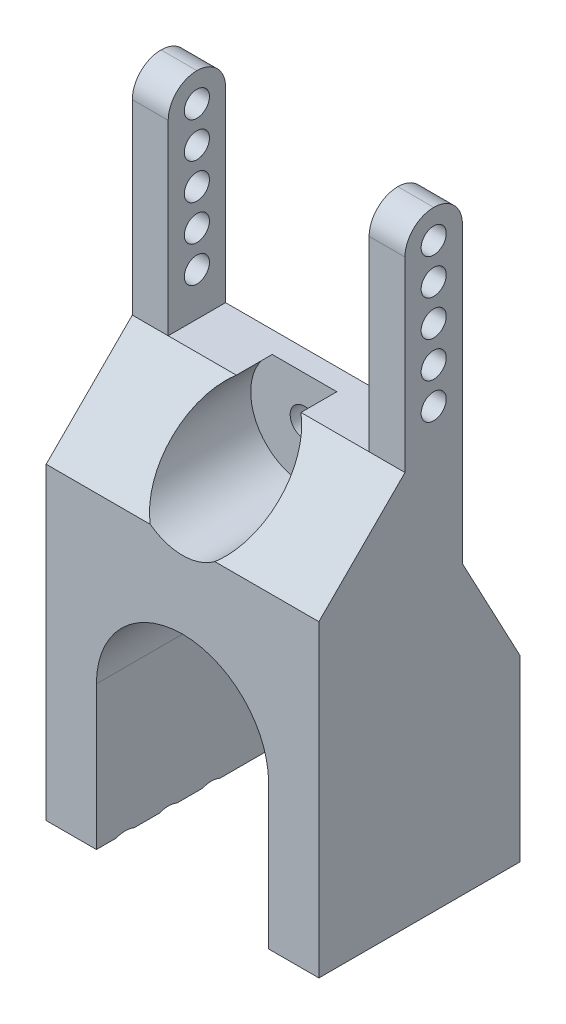
SolidWorks part; units mm, degrees
ref_plane "Front Plane" through (0, 0, 0) normal (0, 0, 1) x (1, 0, 0)
ref_plane "Top Plane" through (0, 0, 0) normal (0, 1, 0) x (1, 0, 0)
ref_plane "Right Plane" through (0, 0, 0) normal (1, 0, 0) x (0, 0, -1)
sketch "Sketch1" plane through (0, 0, 0) normal (0, 0, 1) x (1, 0, 0)
  line L1 (-19, -27.5) -> (19, -27.5)
  line L2 (-19, -27.5) -> (-19, 27.5)
  line L3 (-19, 27.5) -> (19, 27.5)
  line L4 (19, -27.5) -> (19, 27.5)
  line L5 (-19, -27.5) -> (19, 27.5) construction
  line L6 (-19, 27.5) -> (19, -27.5) construction
  point P0 (0, 0)
  dimension "D1" = 38
  dimension "D2" = 55
extrude "Boss-Extrude1" add sketch "Sketch1" along normal blind 20
sketch "Sketch2" plane through (0, 0, 20) normal (0, 0, 1) x (1, 0, 0)
  line L0 (-19, -27.5) -> (19, -27.5) construction
  line L1 (-12, -27.5) -> (12, -27.5)
  line L2 (-12, -27.5) -> (-12, -7.5)
  line L3 (-12, -7.5) -> (12, -7.5) construction
  line L4 (12, -27.5) -> (12, -7.5)
  line L5 (0, -7.5) -> (0, 0) construction
  arc A0 (-12, -7.5) -> (12, -7.5) centre (0, -7.5) cw
  dimension "D1" = 24
  dimension "D2" = 20
extrude "Cut-Extrude1" cut sketch "Sketch2" against normal through all
sketch "Sketch3" plane through (0, -27.5, 0) normal (0, -1, 0) x (1, 0, 0)
  line L0 (-15, 16) -> (15, 16) construction
  line L1 (0, 16) -> (0, 0) construction
  line L2 (12, 20) -> (-12, 20) construction
  circle A0 centre (-15, 16) radius 2.25
  circle A1 centre (15, 16) radius 2.25
  dimension "D1" = 4.5
  dimension "D2" = 30
  dimension "D3" = 4
extrude "Cut-Extrude2" cut sketch "Sketch3" against normal blind 20
pattern_linear "LPattern1" count 3 spacing 6 along (0, 0, -1) of "Cut-Extrude2"
chamfer "Chamfer1" distance 12 angle 45 1 edges at (0, 27.5, 20)
sketch "Sketch4" plane through (0, 27.5, 0) normal (0, 1, 0) x (1, 0, 0)
  line L0 (-19, -8) -> (19, -8) construction
  line L1 (-19, 0) -> (-14, 0)
  line L2 (-19, 0) -> (-19, -8)
  line L3 (-19, -8) -> (-14, -8)
  line L4 (-14, 0) -> (-14, -8)
  dimension "D1" = 5
extrude "Boss-Extrude2" add sketch "Sketch4" along normal blind 30
fillet "Fillet1" radius 4 2 edges at (-16.5, 57.5, 0) (-16.5, 57.5, 8)
sketch "Sketch5" plane through (-19, 0, 0) normal (-1, 0, 0) x (0, 0, 1)
  circle A0 centre (4, 53.5) radius 1.75
  dimension "D1" = 3.5
extrude "Cut-Extrude3" cut sketch "Sketch5" against normal through all
pattern_linear "LPattern2" count 5 spacing 5 along (0, -1, 0) of "Cut-Extrude3"
mirror "Mirror1" about plane through (0, 0, 0) normal (1, 0, 0) of "LPattern2", "Boss-Extrude2", "Fillet1", "Cut-Extrude3"
chamfer "Chamfer2" distance 1 angle 45 6 edges at (15, -27.5, 13.75) (15, -27.5, 7.75) (15, -27.5, 1.75) (-15, -27.5, 1.75) (-15, -27.5, 7.75) (-15, -27.5, 13.75)
sketch "Sketch6" plane through (0, 0, 20) normal (0, 0, 1) x (1, 0, 0)
  line L0 (14, 53.5) -> (-14, 53.5) construction
  line L1 (0, 53.5) -> (0, 21.5) construction
  circle A0 centre (0, 21.5) radius 7.5
  dimension "D2" = 15
  dimension "D1" = 32
extrude "Cut-Extrude4" cut sketch "Sketch6" against normal blind 17
sketch "Sketch7" plane through (0, 0, 3) normal (0, 0, 1) x (1, 0, 0)
  circle A0 centre (0, 21.5) radius 2
  dimension "D1" = 4
extrude "Cut-Extrude5" cut sketch "Sketch7" against normal through all and the other way through all
sketch "Sketch8" plane through (0, 0, 0) normal (0, 0, -1) x (-1, 0, 0)
  line L0 (-12, -27.5) -> (-12, -7.5) construction
  line L1 (-19, -27.5) -> (-12, -27.5)
  line L2 (-19, -27.5) -> (-19, 12.5)
  line L3 (-19, 12.5) -> (-12, 12.5)
  line L4 (-12, -27.5) -> (-12, 12.5)
  line L5 (19, 53.5) -> (19, -27.5) construction
  line L6 (12, -27.5) -> (19, -27.5)
  line L7 (12, -27.5) -> (12, 12.5)
  line L8 (12, 12.5) -> (19, 12.5)
  line L9 (19, -27.5) -> (19, 12.5)
  line L10 (-12, 12.5) -> (12, 12.5) construction
  dimension "D1" = 40
extrude "Boss-Extrude3" add sketch "Sketch8" along normal blind 8
chamfer "Chamfer3" distance 8 angle 62 2 edges at (-15.5, 12.5, -8) (15.5, 12.5, -8) first distance on face at (-15.5, 12.5, -4) first distance on face at (15.5, 12.5, -4)
